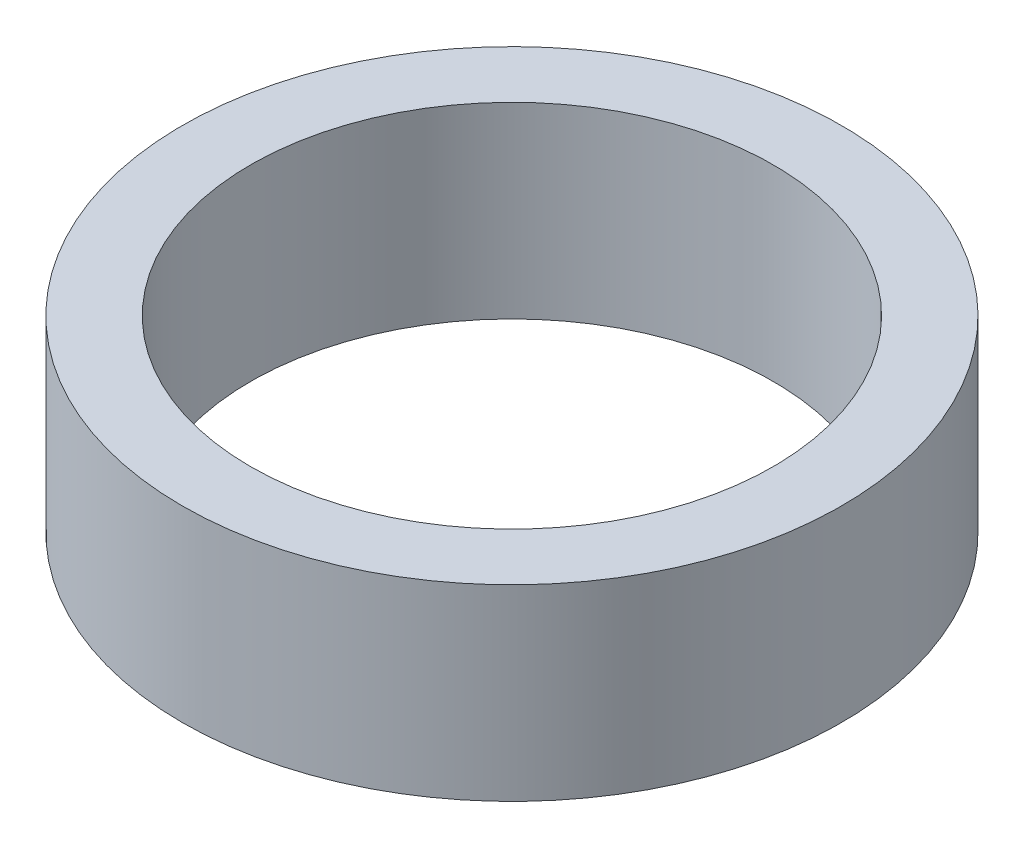
SolidWorks part; units mm, degrees
ref_plane "Front Plane" through (0, 0, 0) normal (0, 0, 1) x (1, 0, 0)
ref_plane "Top Plane" through (0, 0, 0) normal (0, 1, 0) x (1, 0, 0)
ref_plane "Right Plane" through (0, 0, 0) normal (1, 0, 0) x (0, 0, -1)
sketch "Sketch1" plane through (0, 0, 0) normal (0, 1, 0) x (1, 0, 0)
  circle A0 centre (0, 0) radius 290
  dimension "D1" = 580
extrude "Boss-Extrude1" add sketch "Sketch1" along normal blind 165.1
sketch "Sketch2" plane through (0, 165.1, 0) normal (0, 1, 0) x (1, 0, 0)
  circle A0 centre (0, 0) radius 230
  dimension "D1" = 460
extrude "Cut-Extrude1" cut sketch "Sketch2" against normal through all
